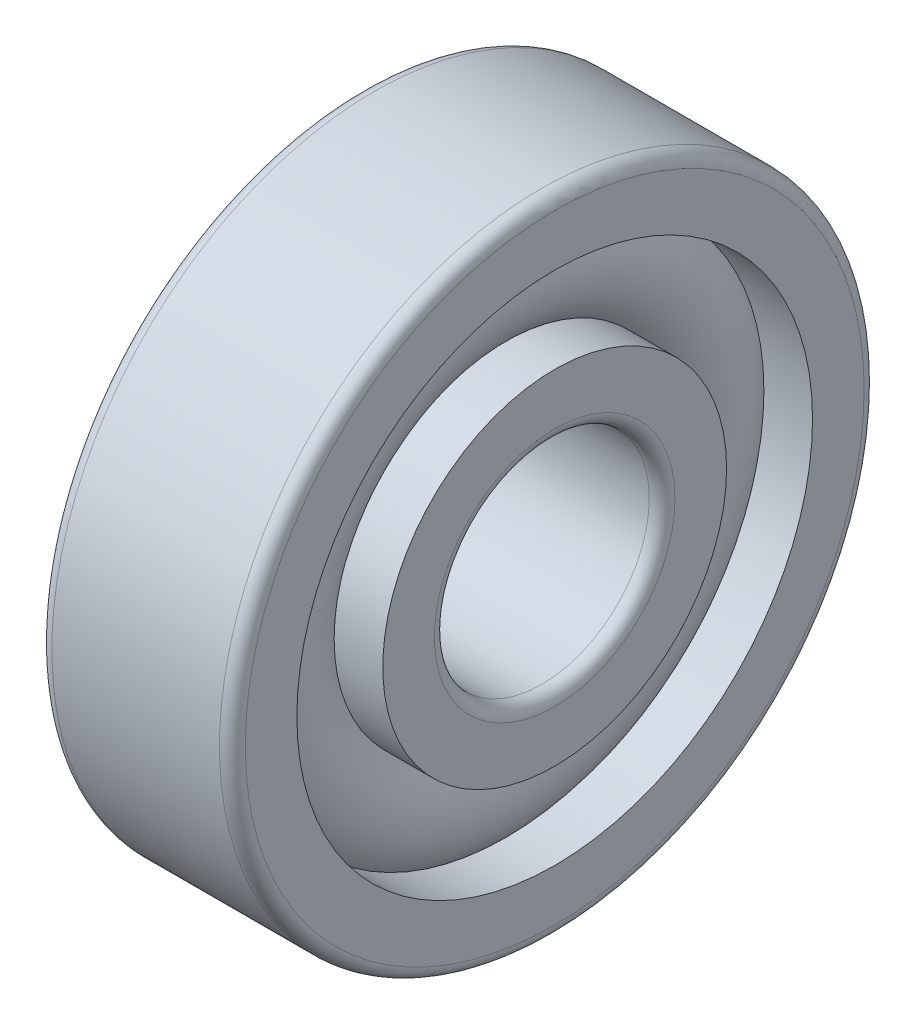
SolidWorks part; units mm, degrees
ref_plane "Plane1" through (0, 0, 0) normal (0, 0, 1) x (1, 0, 0)
ref_plane "Plane2" through (0, 0, 0) normal (0, 1, 0) x (1, 0, 0)
ref_plane "Plane3" through (0, 0, 0) normal (1, 0, 0) x (0, 0, -1)
sketch "Clipboard" plane through (0, 0, 0) normal (0, 0, 1) x (1, 0, 0)
  line L0 (-10, 0) -> (10, 0) construction
  line L1 (0, 0) -> (22.3471, -0.7804)
  line L2 (0, 0) -> (9.9939, 0.349)
  line L3 (0, 0) -> (22.3471, -0.7804)
  line L4 (0, 0) -> (-22.3573, -0.3902)
  dimension "BallCLRad" = 10
sketch "CagSpiSke" plane through (0, 0, 0) normal (0, 0, 1) x (1, 0, 0)
  line L0 (0.3, 9.5) -> (0.3, 10.5)
  line L1 (0.3, 10.5) -> (-0.3, 10.5)
  line L2 (-0.3, 10.5) -> (-0.3, 9.5)
  line L3 (-0.3, 9.5) -> (0.3, 9.5)
  line L4 (-20.6375, 0) -> (20.6375, 0) construction
  line L5 (0, 0) -> (0, 23.7692) construction
  dimension "OD" = 21
  dimension "ID" = 19
revolve "CageSpine" add sketch "CagSpiSke" angle 0.001 about L4 reverse direction yes
ref_axis "Axis1" through (-50, 0, 0) along (1, 0, 0)
sketch "CagBalSke" plane through (0, 0, 0) normal (0, 0, 1) x (1, 0, 0)
  line L0 (-3.3, 10) -> (3.3, 10)
  line L1 (-1.905, 10) -> (1.905, 10) construction
  line L2 (-10, 0) -> (10, 0) construction
  line L3 (0, 0) -> (0, 24) construction
  arc A0 (3.3, 10) -> (-3.3, 10) centre (0, 10) cw
  dimension "BallCLRad" = 10
revolve "CageBall" [suppressed] add sketch "CagBalSke" angle 360 about L1 reverse direction yes
pattern_circular "CageBalls" [suppressed] count 2 every 180 about axis through (-50, 0, 0) along (1, 0, 0)
sketch "CagTrmODSke" plane through (0, 0, 0) normal (0, 0, 1) x (1, 0, 0)
  line L0 (3.301, 10.5) -> (3.301, 13.301)
  line L1 (3.301, 13.301) -> (-3.301, 13.301)
  line L2 (-3.301, 13.301) -> (-3.301, 10.5)
  line L3 (-3.301, 10.5) -> (3.301, 10.5)
  line L4 (-20.6375, 0) -> (20.6375, 0) construction
  line L5 (0, 0) -> (0, 25) construction
  dimension "Width" = 6.602
  dimension "ID" = 21
  dimension "OD" = 26.602
revolve "CageTrimOD" [suppressed] cut sketch "CagTrmODSke" angle 360 about L4 reverse direction yes
sketch "CagTrmIDSke" plane through (0, 0, 0) normal (0, 0, 1) x (1, 0, 0)
  line L0 (3.301, 6.701) -> (3.301, 9.5)
  line L1 (3.301, 9.5) -> (-3.301, 9.5)
  line L2 (-3.301, 9.5) -> (-3.301, 6.701)
  line L3 (-3.301, 6.701) -> (3.301, 6.701)
  line L4 (-20.6375, 0) -> (20.6375, 0) construction
  line L5 (0, 0) -> (0, 25) construction
  dimension "Width" = 6.602
  dimension "ID" = 13.402
  dimension "OD" = 19
revolve "CageTrimID" [suppressed] cut sketch "CagTrmIDSke" angle 360 about L4 reverse direction yes
sketch "BalSimSke" plane through (0, 0, 0) normal (0, 0, 1) x (1, 0, 0)
  line L0 (-10, 0) -> (10, 0) construction
  line L1 (-10, 10) -> (10, 10) construction
  line L2 (0, 0) -> (0, 23) construction
  circle A0 centre (0, 10) radius 3
  dimension "BallCLRad" = 10
  dimension "Ball_diameter" = 6
revolve "BallsSimplified" add sketch "BalSimSke" angle 360 about L0
sketch "BalDetSke" plane through (0, 0, 0) normal (0, 0, 1) x (1, 0, 0)
  line L0 (-3, 10) -> (3, 10)
  line L1 (-1.905, 10) -> (1.905, 10) construction
  line L2 (0, 0) -> (0, 25) construction
  arc A0 (3, 10) -> (-3, 10) centre (0, 10) cw
  dimension "BallCLRad" = 10
  dimension "Ball_diameter" = 6
revolve "BallDetailed" [suppressed] add sketch "BalDetSke" angle 360 about L1 reverse direction yes
sketch "InnRacSke" plane through (0, 0, 0) normal (0, 0, 1) x (1, 0, 0)
  line L0 (-2.2024, 8) -> (-4.5, 8)
  line L1 (-4.5, 8) -> (-4.5, 5.6)
  line L2 (-3.9, 5) -> (3.9, 5)
  line L3 (4.5, 5.6) -> (4.5, 8)
  line L4 (4.5, 8) -> (2.2024, 8)
  line L5 (-20.6375, 0) -> (20.6375, 0) construction
  line L6 (0, 0) -> (0, 30) construction
  arc A0 (-4.5, 5.6) -> (-3.9, 5) centre (-3.9, 5.6) ccw
  arc A1 (3.9, 5) -> (4.5, 5.6) centre (3.9, 5.6) ccw
  arc A2 (2.2024, 8) -> (-2.2024, 8) centre (0, 10) cw
  dimension "BallCLRad" = 10
  dimension "Fillet_radius" = 0.6
  dimension "Ball_diameter" = 5.95
  dimension "ID" = 10
  dimension "OD" = 16
  dimension "Width" = 9
revolve "InnerRace" add sketch "InnRacSke" angle 360 about L5 reverse direction yes
sketch "OutRacSke" plane through (0, 0, 0) normal (0, 0, 1) x (1, 0, 0)
  line L0 (-2.2024, 12) -> (-4.5, 12)
  line L1 (-4.5, 12) -> (-4.5, 14.4)
  line L2 (-3.9, 15) -> (3.9, 15)
  line L3 (4.5, 14.4) -> (4.5, 12)
  line L4 (4.5, 12) -> (2.2024, 12)
  line L5 (-20.6375, 0) -> (20.6375, 0) construction
  line L6 (0, 0) -> (0, 30) construction
  arc A0 (-4.5, 14.4) -> (-3.9, 15) centre (-3.9, 14.4) cw
  arc A1 (3.9, 15) -> (4.5, 14.4) centre (3.9, 14.4) cw
  arc A2 (2.2024, 12) -> (-2.2024, 12) centre (0, 10) ccw
  dimension "BallCLRad" = 10
  dimension "Fillet_radius" = 0.6
  dimension "Ball_diameter" = 5.95
  dimension "Width" = 9
revolve "OuterRace" add sketch "OutRacSke" angle 360 about L5 reverse direction yes
pattern_circular "BallsDetailed" [suppressed] count 2 every 180 about axis through (-50, 0, 0) along (1, 0, 0)
equation "\"BallCLRad@Clipboard\" = ( \"OD@OutRacSke\" + \"ID@InnRacSke\" ) / 4"
equation "\"BallCLRad@BalSimSke\" = \"BallCLRad@Clipboard\""
equation "\"BallCLRad@BalDetSke\" = \"BallCLRad@Clipboard\""
equation "\"BallCLRad@InnRacSke\" = \"BallCLRad@Clipboard\""
equation "\"BallCLRad@OutRacSke\" = \"BallCLRad@Clipboard\""
equation "\"Ball_diameter@InnRacSke\" = \"Ball_diameter@BalDetSke\" - 0.05"
equation "\"Ball_diameter@OutRacSke\" = \"Ball_diameter@BalDetSke\" - 0.05"
equation "\"Ball_diameter@BalSimSke\" = \"Ball_diameter@BalDetSke\""
equation "\"Width@OutRacSke\" = \"Width@InnRacSke\""
equation "\"Fillet_radius@OutRacSke\" = \"Fillet_radius@InnRacSke\""
equation "\"Max_count@Clipboard\" = int( 3.14159265 / atn(( \"Ball_diameter@BalDetSke\" / 2) / sqr( \"BallCLRad@Clipboard\"  *  \"BallCLRad@Clipboard\" - ( \"Ball_diameter@BalDetSke\" / 2) *  ( \"Ball_diameter@BalDetSke\" / 2))))"
equation "\"Max_count@Clipboard\" = ((sgn( \"Max_count@Clipboard\" - \"Count@Clipboard\" )-1)*( \"Max_count@Clipboard\" - \"Count@Clipboard\" ))/-2+ \"Count@Clipboard\""
equation "\"Count@BallsDetailed\" = int( \"Show_count@Clipboard\" ) "
equation "\"Count@BallsDetailed\" = ((sgn( \"Count@BallsDetailed\" - \"Max_count@Clipboard\" )-1)*( \"Count@BallsDetailed\" - \"Max_count@Clipboard\" ))/-2+ \"Max_count@Clipboard\""
equation "\"Count@BallsDetailed\" = ((sgn( \"Count@BallsDetailed\" - \"Min_count@Clipboard\" )+1)*( \"Count@BallsDetailed\" - \"Min_count@Clipboard\"))/2 +\"Min_count@Clipboard\""
equation "\"Angle@BallsDetailed\" = 360.0 / \"Max_count@Clipboard\""
equation "\"BallCLRad@CagBalSke\" = \"BallCLRad@Clipboard\""
equation "\"Count@CageBalls\" = \"Count@BallsDetailed\""
equation "\"Angle@CageBalls\" = \"Angle@BallsDetailed\""
equation "\"Angle@CageSpine\" =  \"Angle@CageBalls\" * ( \"Count@CageBalls\" -1 + int( \"Count@CageBalls\" / \"Max_count@Clipboard\" ) )  + 0.001 -  int( \"Count@CageBalls\" / \"Max_count@Clipboard\" ) * 0.001"
equation "\"Angle@CageSpine\" =  \"Angle@CageSpine\" * int( \"Min_count@Clipboard\" / 2) + int(1 / \"Min_count@Clipboard\")  * 0.001"
equation "\"CageWallOD@CagBalSke\" =  \"Ball_diameter@BalDetSke\" * 1.1"
equation "\"Thickness@CagSpiSke\" =  \"Ball_diameter@BalDetSke\" * 0.1"
equation "\"OD@CagTrmODSke\" = \"BallCLRad@Clipboard\" * 2 + \"CageWallOD@CagBalSke\" + 0.002"
equation "\"ID@CagTrmODSke\" = \"BallCLRad@Clipboard\" * 2 + \"Ball_diameter@BalDetSke\" / 6"
equation "\"OD@CagTrmIDSke\" = \"BallCLRad@Clipboard\" * 2 - \"Ball_diameter@BalDetSke\" / 6"
equation "\"ID@CagTrmIDSke\" = \"BallCLRad@Clipboard\" * 2 - \"CageWallOD@CagBalSke\" + 0.002"
equation "\"OD@CagSpiSke\" = \"ID@CagTrmODSke\""
equation "\"ID@CagSpiSke\" = \"OD@CagTrmIDSke\""
equation "\"Width@CagTrmODSke\" = \"CageWallOD@CagBalSke\" + 0.002"
equation "\"Width@CagTrmIDSke\" = \"CageWallOD@CagBalSke\" + 0.002"
